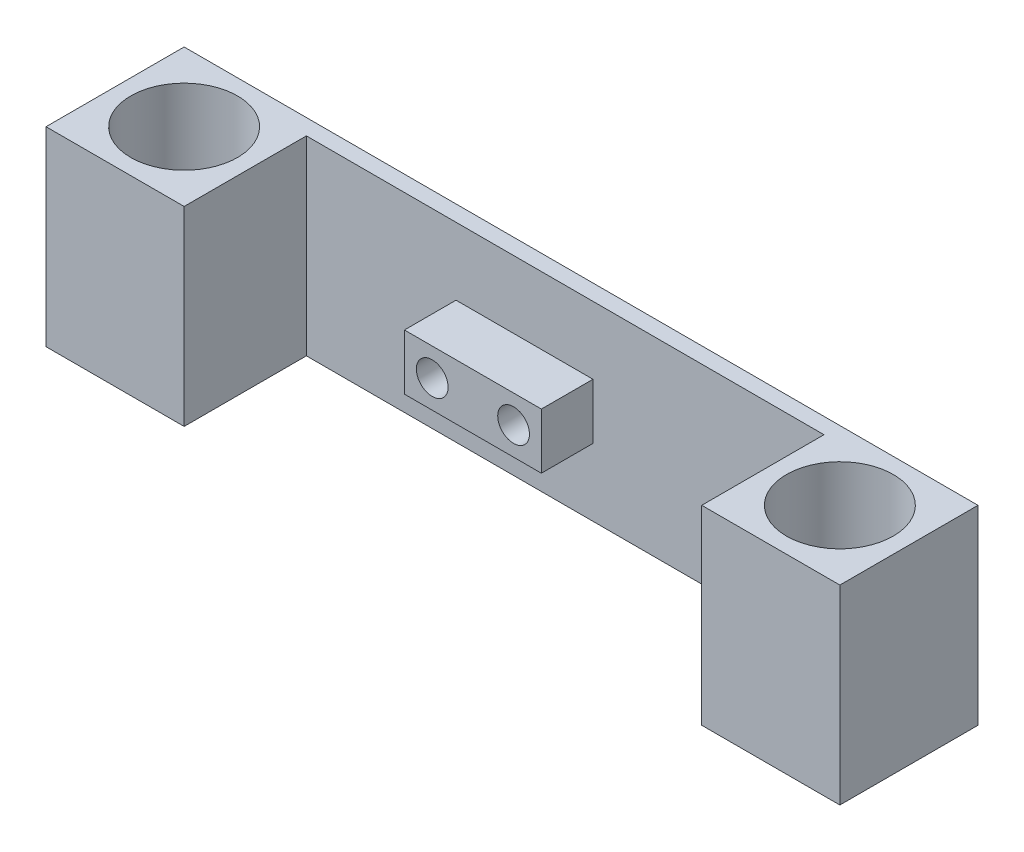
SolidWorks part; units mm, degrees
ref_plane "Front Plane" through (0, 0, 0) normal (0, 0, 1) x (1, 0, 0)
ref_plane "Top Plane" through (0, 0, 0) normal (0, 1, 0) x (1, 0, 0)
ref_plane "Right Plane" through (0, 0, 0) normal (1, 0, 0) x (0, 0, -1)
sketch "Sketch1" plane through (0, 0, 0) normal (0, 1, 0) x (1, 0, 0)
  line L1 (-17.4, 17.4) -> (17.4, 17.4)
  line L2 (-17.4, 13.4) -> (-17.4, -17.4)
  line L3 (-17.4, -17.4) -> (17.4, -17.4)
  line L4 (17.4, 17.4) -> (17.4, -17.4)
  line L5 (0, -17.4) -> (0, 17.4) construction
  line L6 (-17.4, 0) -> (17.4, 0) construction
  line L7 (-17.4, 17.4) -> (-82.6, 17.4)
  line L9 (-17.4, 13.4) -> (-82.6, 13.4)
  line L10 (-82.6, 17.4) -> (-82.6, 13.4)
  circle A0 centre (0, 0) radius 13.45
  dimension "D1" = 26.9
  dimension "D2" = 34.8
  dimension "D3" = 34.8
  dimension "D4" = 65.2
  dimension "D5" = 4
extrude "Boss-Extrude2" add sketch "Sketch1" along normal blind 48
mirror "Mirror2" about plane through (-82.6, 48, -17.4) normal (1, 0, 0) of "Boss-Extrude2"
sketch "Sketch7" plane through (0, 0, -13.4) normal (0, 0, 1) x (1, 0, 0)
  line L0 (-147.8, 24) -> (-17.4, 24) construction
  line L1 (-147.8, 48) -> (-147.8, 0) construction
  line L2 (-17.4, 48) -> (-17.4, 0) construction
  line L3 (-82.6, 48) -> (-82.6, 0) construction
  line L4 (-147.8, 48) -> (-17.4, 48) construction
  line L5 (-147.8, 0) -> (-17.4, 0) construction
  line L6 (-103.1, 24) -> (-82.6, 24) construction
  line L8 (-110.1, 17) -> (-75.6, 17)
  line L9 (-110.1, 17) -> (-110.1, 31)
  line L10 (-110.1, 31) -> (-75.6, 31)
  line L11 (-75.6, 17) -> (-75.6, 31)
  line L12 (-92.85, 31) -> (-92.85, 17) construction
  line L13 (-110.1, 24) -> (-75.6, 24) construction
  circle A0 centre (-82.6, 24) radius 4
  circle A2 centre (-103.1, 24) radius 4
  point P15 (-92.85, 24)
  dimension "D1" = 8
  dimension "D3" = 8
  dimension "D5" = 20.5
  dimension "D2" = 14
  dimension "D4" = 34.5
extrude "Boss-Extrude3" add sketch "Sketch7" along normal blind 13
